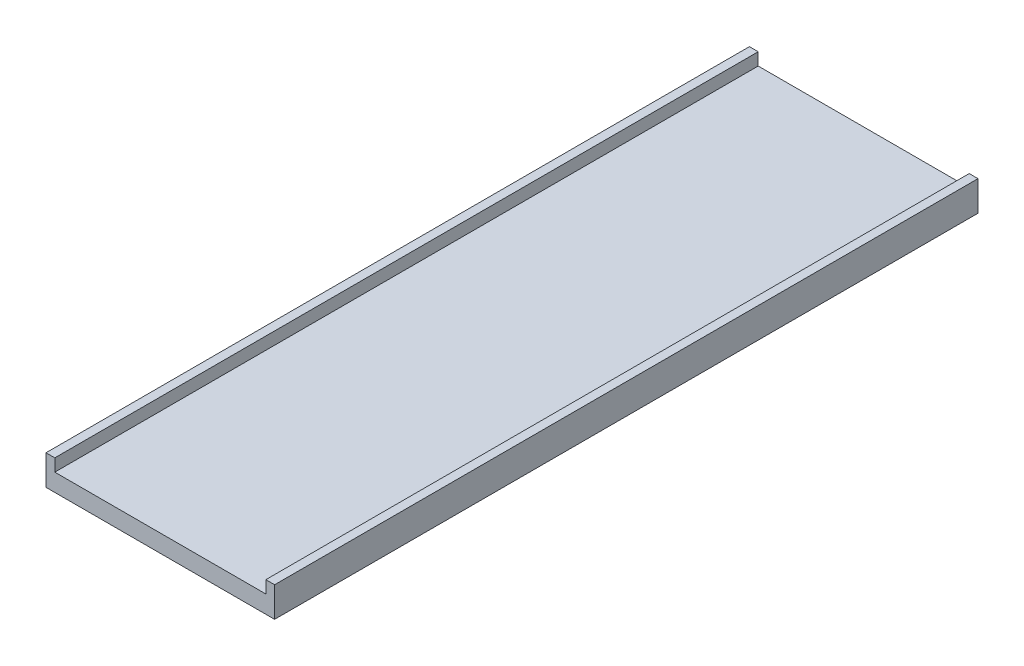
SolidWorks part; units mm, degrees
ref_plane "Front Plane" through (0, 0, 0) normal (0, 0, 1) x (1, 0, 0)
ref_plane "Top Plane" through (0, 0, 0) normal (0, 1, 0) x (1, 0, 0)
ref_plane "Right Plane" through (0, 0, 0) normal (1, 0, 0) x (0, 0, -1)
sketch "Sketch1" plane through (0, 0, 0) normal (0, 0, 1) x (1, 0, 0)
  line L0 (0, 0) -> (25, 0)
  line L1 (25, 0) -> (25, -35.2361)
  line L2 (25, -35.2361) -> (625, -35.2361)
  line L3 (625, -35.2361) -> (625, 0)
  line L4 (625, 0) -> (650, 0)
  line L5 (650, 0) -> (650, -85.2361)
  line L6 (650, -85.2361) -> (0, -85.2361)
  line L7 (0, -85.2361) -> (0, 0)
  line L8 (-2000, 0) -> (-2000, 547.1361)
  dimension "D1" = 25
  dimension "D2" = 35.2361
  dimension "D3" = 650
  dimension "D4" = 50
  dimension "D5" = 2000
extrude "Boss-Extrude1" add sketch "Sketch1" along normal blind 2000 contours L2 L3 L4 L5 L6 L7 L0 L1
